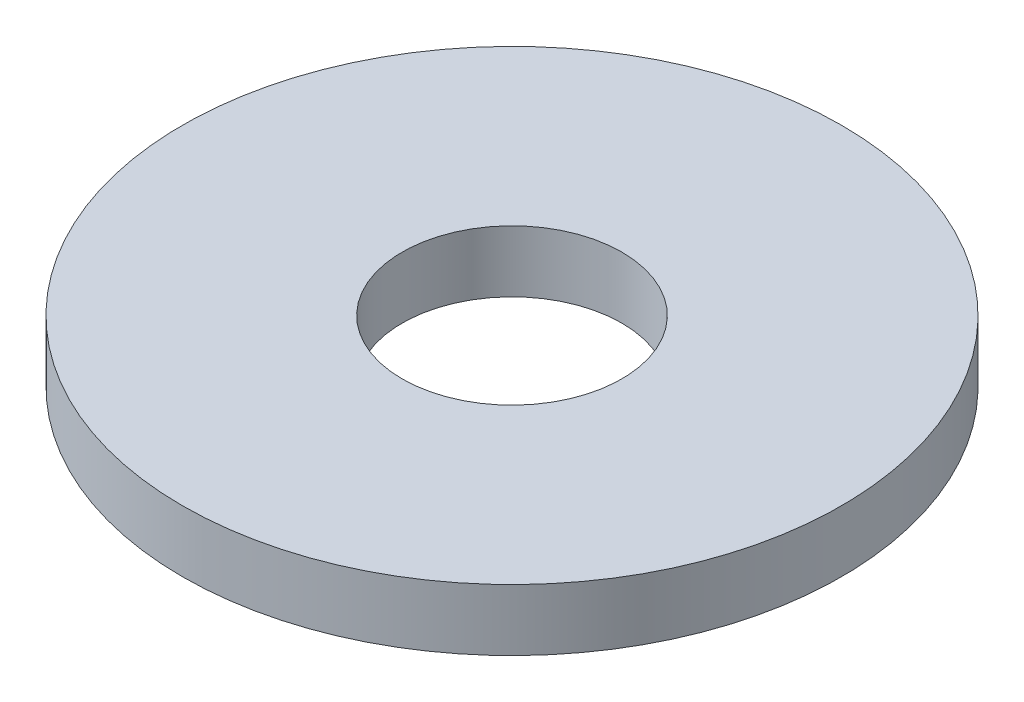
SolidWorks part; units mm, degrees
ref_plane "Front Plane" through (0, 0, 0) normal (0, 0, 1) x (1, 0, 0)
ref_plane "Top Plane" through (0, 0, 0) normal (0, 1, 0) x (1, 0, 0)
ref_plane "Right Plane" through (0, 0, 0) normal (1, 0, 0) x (0, 0, -1)
sketch "Sketch1" plane through (0, 0, 0) normal (0, 1, 0) x (1, 0, 0)
  circle A0 centre (0, 0) radius 75
  dimension "FLANGE_OD" = 150
extrude "Boss-Extrude1" add sketch "Sketch1" along normal blind 14
sketch "Sketch2" plane through (0, 0, 0) normal (0, 1, 0) x (1, 0, 0)
  circle A0 centre (0, 0) radius 25
  dimension "BORE_D" = 50
extrude "Cut-Extrude1" cut sketch "Sketch2" along normal through all
sketch "Sketch3" plane through (0, 14, 0) normal (0, 1, 0) x (1, 0, 0)
  circle A0 centre (0, 0) radius 17.9896 construction
  circle A1 centre (-17.9896, 0) radius 5.2001
  dimension "BOLT_D" = 10.4002
  dimension "BOLT_PCD" = 35.9792
extrude "Cut-Extrude2" cut sketch "Sketch3" against normal blind 12.9083 rebuild error yes
pattern_circular "CirPattern1" count 8 over 360 rebuild error yes
